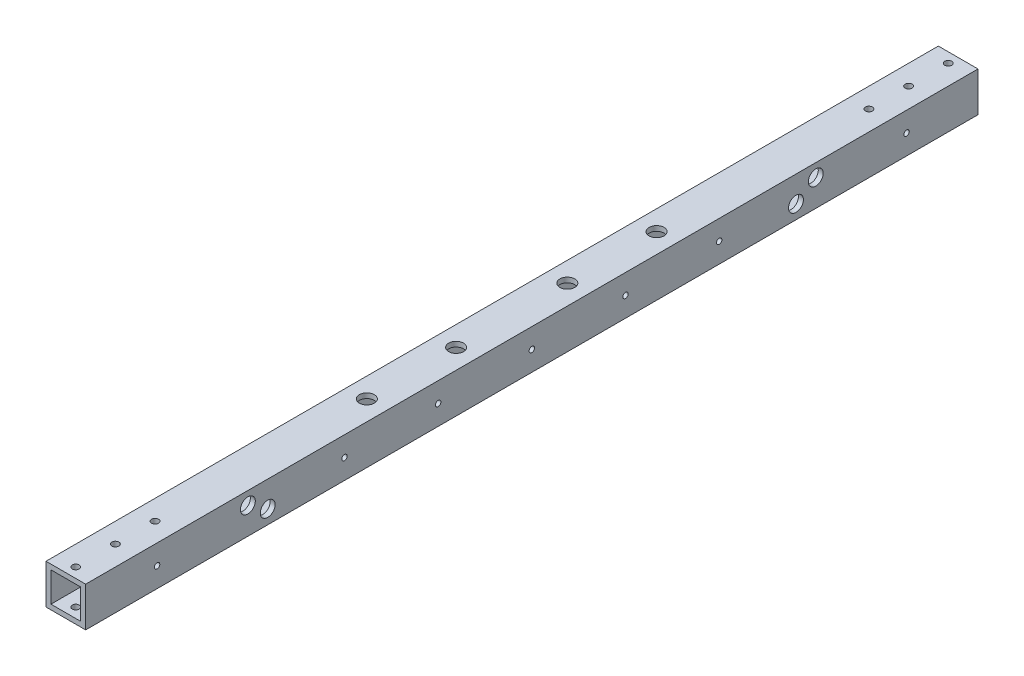
SolidWorks part; units mm, degrees
material "6061-T6 (SS)"
ref_plane "Front Plane" through (0, 0, 0) normal (0, 0, 1) x (1, 0, 0)
ref_plane "Top Plane" through (0, 0, 0) normal (0, 1, 0) x (1, 0, 0)
ref_plane "Right Plane" through (0, 0, 0) normal (1, 0, 0) x (0, 0, -1)
sketch "Sketch1" plane through (0, 0, 0) normal (0, 0, 1) x (1, 0, 0)
  line L1 (-12.7, -12.7) -> (12.7, -12.7)
  line L2 (-12.7, -12.7) -> (-12.7, 12.7)
  line L3 (-12.7, 12.7) -> (12.7, 12.7)
  line L4 (12.7, -12.7) -> (12.7, 12.7)
  line L5 (-12.7, -12.7) -> (12.7, 12.7) construction
  line L6 (-12.7, 12.7) -> (12.7, -12.7) construction
  point P0 (0, 0)
  dimension "D1" = 25.4
  dimension "D2" = 25.4
extrude "Extrude-Thin1" add sketch "Sketch1" along normal blind 571.5 thin thin type one direction reverse wall 3.175
hole_wizard "#8 Clearance Hole1" positions "3DSketch1" profile "Sketch3" hole size "#8" standard "ANSI Inch" end condition through all
sketch3d "3DSketch1"
  line L1 (12.7, 12.7, 0) -> (-12.7, 12.7, 0) construction
  line L6 (0, 12.7, 571.5) -> (0, 12.7, 0) construction
  line L7 (12.7, 12.7, 571.5) -> (-12.7, 12.7, 571.5) construction
  point P57 (0, 12.7, 6.35)
  point P59 (0, 12.7, 31.75)
  point P61 (0, 12.7, 57.15)
  point P63 (0, 12.7, 539.75)
  point P65 (0, 12.7, 514.35)
  point P67 (0, 12.7, 565.15)
  dimension "D1" = 25.4
  dimension "D2" = 25.4
  dimension "D3" = 6.35
  dimension "D4" = 25.4
  dimension "D5" = 25.4
  dimension "D6" = 6.35
sketch "Sketch3" plane through (0, 12.7, 565.15) normal (1, 0, 0) x (0, 0, 1)
  line L0 (0, 0) -> (0, 25.4)
  line L1 (0, 25.4) -> (2.2479, 25.4)
  line L2 (2.2479, 25.4) -> (2.2479, 0)
  line L5 (2.2479, 0) -> (0, 0)
  line L11 (0, -6.35) -> (0, 107.95) construction
  dimension "Thru Hole Dia." = 4.4958
  dimension "Thru Hole Depth" = 25.4
hole_wizard "#8-32 Tapped Hole1" positions "Sketch8" profile "Sketch9" tap size "#8-32" standard "ANSI Inch"
sketch "Sketch8" plane through (12.7, -82.55, 285.75) normal (1, 0, 0) x (0, 0, -1)
  point P0 (-240, 82.55)
  point P6 (-120, 82.55)
  point P9 (-60, 82.55)
  point P12 (0, 82.55)
  point P15 (60, 82.55)
  point P18 (120, 82.55)
  point P24 (240, 82.55)
sketch "Sketch9" plane through (12.7, 0, 525.75) normal (0, 1, 0) x (0, 0, -1)
  line L0 (0, 0) -> (0, 13.3314)
  line L1 (0, 13.3314) -> (1.7272, 12.2936)
  line L2 (1.7272, 12.2936) -> (1.7272, 0)
  line L3 (1.7272, 0) -> (0, 0)
  line L4 (0, 13.3314) -> (-1.7272, 12.2936) construction
  line L5 (0, -6.35) -> (0, 107.95) construction
  dimension "Tap Drill Dia." = 3.4544
  dimension "Tap Drill Depth" = 12.2936
  dimension "Drill Angle" = 118
hole_wizard "3/8 (0.375) Diameter Hole2" positions "Sketch12" profile "Sketch13" hole size "3/8" standard "ANSI Inch" end condition through all
sketch "Sketch12" plane through (-12.7, -82.55, 285.75) normal (1, 0, 0) x (0, 0, -1)
  point P0 (-181.864, 86.995)
  point P3 (-169.164, 78.74)
  point P6 (169.164, 78.74)
  point P9 (181.864, 86.995)
  point P12 (181.864, 57.15)
  point P15 (-181.864, 57.15)
sketch "Sketch13" plane through (-12.7, 4.445, 467.614) normal (0, 1, 0) x (0, 0, 1)
  line L0 (0, 0) -> (0, 25.4)
  line L1 (0, 25.4) -> (4.7625, 25.4)
  line L2 (4.7625, 25.4) -> (4.7625, 0)
  line L3 (4.7625, 0) -> (0, 0)
  line L4 (0, -6.35) -> (0, 107.95) construction
  dimension "Thru Hole Dia." = 9.525
  dimension "Thru Hole Depth" = 25.4
hole_wizard "3/8 (0.375) Diameter Hole3" positions "Sketch14" profile "Sketch15" hole size "3/8" standard "ANSI Inch" end condition through all
sketch "Sketch14" plane through (-346.075, 12.7, 285.75) normal (0, 1, 0) x (0, 0, 1)
  point P9 (-92.583, 346.075)
  point P12 (-35.433, 346.075)
  point P18 (35.814, 346.075)
  point P21 (92.964, 346.075)
  point P24 (-22.9616, -346.775)
  point P27 (50.0634, -346.775)
  point P30 (123.0884, -346.775)
  point P33 (-381, 114.3)
  point P36 (-381, 98.425)
  point P39 (-381, 82.55)
  point P42 (-381, -114.3)
  point P45 (-381, -130.175)
  point P48 (-381, -146.05)
sketch "Sketch15" plane through (0, 12.7, 193.167) normal (1, 0, 0) x (0, 0, 1)
  line L0 (0, 0) -> (0, 25.4)
  line L1 (0, 25.4) -> (4.7625, 25.4)
  line L2 (4.7625, 25.4) -> (4.7625, 0)
  line L3 (4.7625, 0) -> (0, 0)
  line L4 (0, -6.35) -> (0, 107.95) construction
  dimension "Thru Hole Dia." = 9.525
  dimension "Thru Hole Depth" = 25.4
